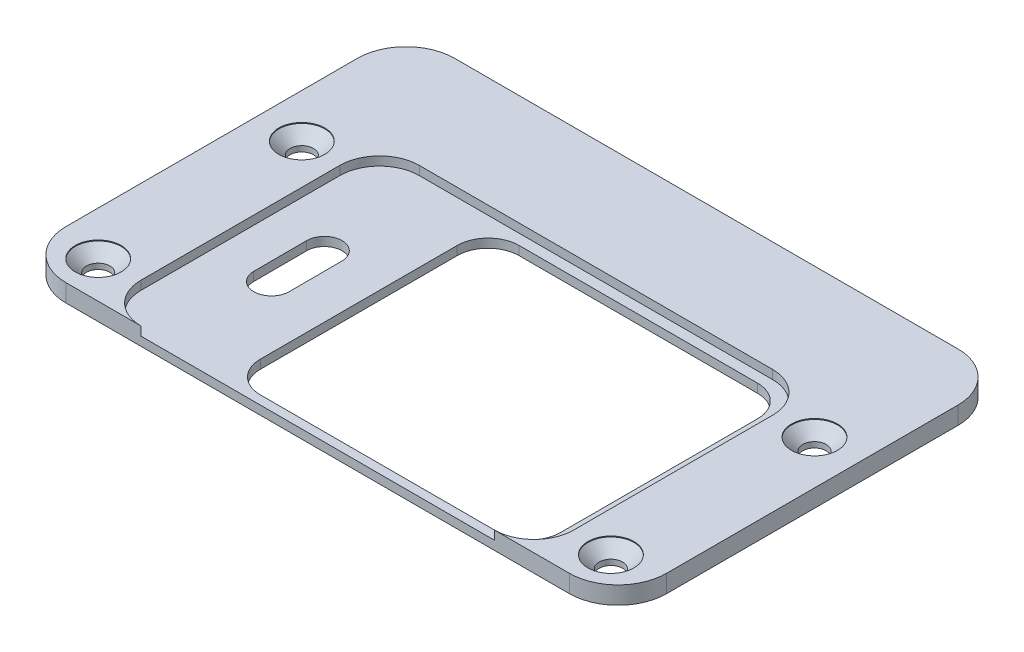
SolidWorks part; units mm, degrees
ref_plane "前视基准面" through (0, 0, 0) normal (0, 0, 1) x (1, 0, 0)
ref_plane "上视基准面" through (0, 0, 0) normal (0, 1, 0) x (1, 0, 0)
ref_plane "右视基准面" through (0, 0, 0) normal (1, 0, 0) x (0, 0, -1)
other "Configuration Table"
sketch "草图1" plane through (0, 0, 0) normal (0, 1, 0) x (1, 0, 0)
  line L1 (-10.0242, 18.5386) -> (57.9758, 18.5386)
  line L2 (-10.0242, 18.5386) -> (-10.0242, -25.4614)
  line L3 (-10.0242, -25.4614) -> (57.9758, -25.4614)
  line L4 (57.9758, 18.5386) -> (57.9758, -25.4614)
  dimension "D1" = 68
  dimension "D2" = 44
extrude "凸台-拉伸1" add sketch "草图1" along normal blind 2
fillet "圆角1" radius 5.5 4 edges at (-10.0242, 1, -18.5386) (57.9758, 1, -18.5386) (57.9758, 1, 25.4614) (-10.0242, 1, 25.4614)
sketch "草图3" plane through (0, 2, 0) normal (0, 1, 0) x (1, 0, 0)
  line L0 (57.9758, -19.9614) -> (57.9758, 13.0386) construction
  line L1 (3.9758, 6.0386) -> (43.9758, 6.0386)
  line L2 (-0.5242, 1.5386) -> (-0.5242, -20.9614)
  line L3 (3.9758, -25.4614) -> (43.9758, -25.4614)
  line L4 (48.4758, 1.5386) -> (48.4758, -20.9614)
  line L5 (-10.0242, 13.0386) -> (-10.0242, -19.9614) construction
  arc A0 (43.9758, 6.0386) -> (48.4758, 1.5386) centre (43.9758, 1.5386) cw
  arc A1 (43.9758, -25.4614) -> (48.4758, -20.9614) centre (43.9758, -20.9614) ccw
  arc A2 (-0.5242, -20.9614) -> (3.9758, -25.4614) centre (3.9758, -20.9614) ccw
  arc A3 (3.9758, 6.0386) -> (-0.5242, 1.5386) centre (3.9758, 1.5386) ccw
  point P4 (5.5026, 5.821)
  point P5 (52.4758, -25.4614)
  point P12 (48.4758, -25.4614)
  point P15 (-0.5242, -25.4614)
  dimension "D3" = 4.5
  dimension "D1" = 9.5
  dimension "D2" = 9.5
  dimension "D4" = 31.5
extrude "切除-拉伸1" cut sketch "草图3" against normal blind 1
sketch "草图4" plane through (0, 1, 0) normal (0, 1, 0) x (1, 0, 0)
  line L0 (57.9758, -19.9614) -> (57.9758, 13.0386) construction
  line L1 (43.4758, -24.4614) -> (16.4758, -24.4614)
  line L2 (46.9758, -20.9614) -> (46.9758, 1.3386)
  line L3 (43.4758, 4.8386) -> (16.4758, 4.8386)
  line L4 (12.9758, -20.9614) -> (12.9758, 1.3386)
  line L5 (3.9758, -25.4614) -> (43.9758, -25.4614) construction
  arc A0 (46.9758, 1.3386) -> (43.4758, 4.8386) centre (43.4758, 1.3386) ccw
  arc A1 (43.4758, -24.4614) -> (46.9758, -20.9614) centre (43.4758, -20.9614) ccw
  arc A2 (16.4758, 4.8386) -> (12.9758, 1.3386) centre (16.4758, 1.3386) ccw
  arc A3 (16.4758, -24.4614) -> (12.9758, -20.9614) centre (16.4758, -20.9614) cw
  point P10 (46.9758, 4.8386)
  point P13 (46.9758, -24.4614)
  point P18 (12.9758, -24.4614)
  dimension "D5" = 3.5
  dimension "D1" = 29.3
  dimension "D2" = 34
  dimension "D3" = 11
  dimension "D4" = 1
extrude "切除-拉伸2" cut sketch "草图4" against normal blind 1
sketch "草图5" plane through (0, 2, 0) normal (0, 1, 0) x (1, 0, 0)
  circle A0 centre (53.0008, -21.2864) radius 1.325
  circle A1 centre (53.0008, 1.7636) radius 1.325
  circle A2 centre (-5.0492, 1.7636) radius 1.325
  circle A3 centre (-5.0492, -21.2864) radius 1.325
  dimension "D1" = 2.65
extrude "切除-拉伸3" cut sketch "草图5" against normal up to next
sketch "草图6" plane through (0, 2, 0) normal (0, 1, 0) x (1, 0, 0)
  circle A0 centre (-5.0492, 1.7636) radius 2.6
  circle A1 centre (-5.0492, -21.2864) radius 2.6
  circle A2 centre (53.0008, 1.7636) radius 2.6
  circle A3 centre (53.0008, -21.2864) radius 2.6
  dimension "D1" = 5.2
sketch "草图7" plane through (0, 1, 0) normal (0, 1, 0) x (1, 0, 0)
  line L0 (5.9758, -6.7114) -> (5.9943, -12.7195) construction
  line L1 (7.9758, -6.7052) -> (7.9943, -12.7133)
  line L2 (3.9759, -6.7175) -> (3.9943, -12.7256)
  arc A0 (7.9758, -6.7052) -> (3.9759, -6.7175) centre (5.9758, -6.7114) ccw
  arc A1 (3.9943, -12.7256) -> (7.9943, -12.7133) centre (5.9943, -12.7195) ccw
  point P4 (5.9851, -9.7154)
  dimension "D1" = 2
extrude "切除-拉伸5" cut sketch "草图7" against normal through all
extrude "切除-拉伸6" cut sketch "草图6" against normal blind 1.5
chamfer "倒角2" distance 1.4 angle 45 4 edges at (53.0008, 0.5, 23.8864) (-5.0492, 0.5, 23.8864) (-5.0492, 0.5, 0.8364) (53.0008, 0.5, 0.8364)
